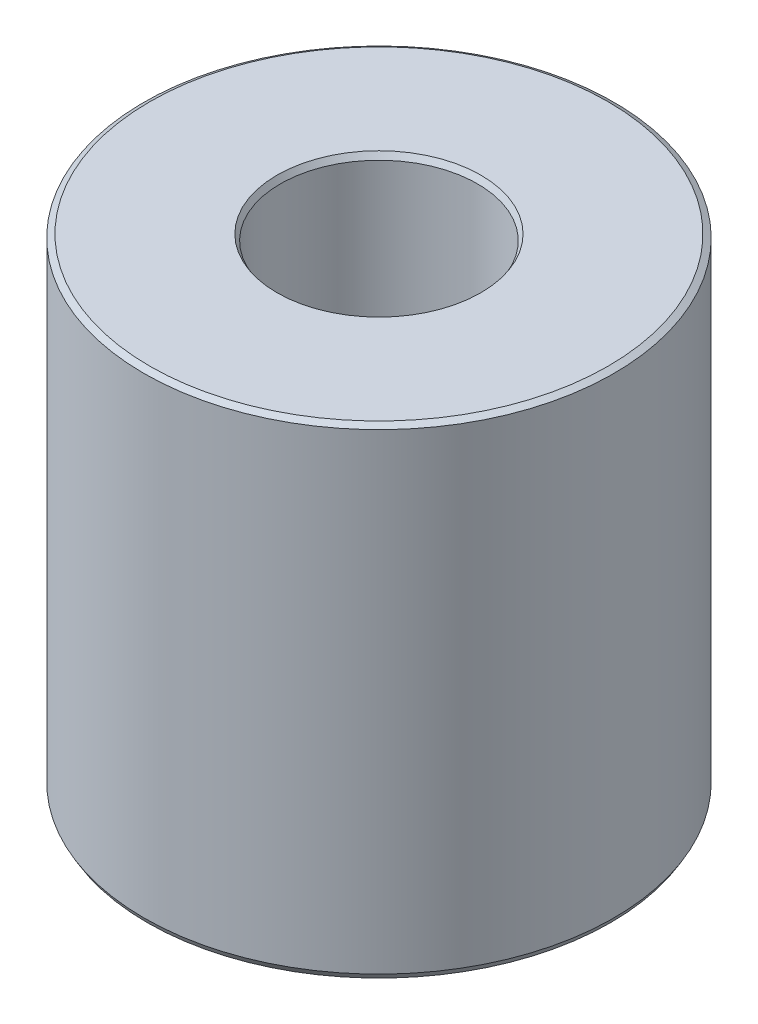
SolidWorks part; units mm, degrees
ref_plane "Front Plane" through (0, 0, 0) normal (0, 0, 1) x (1, 0, 0)
ref_plane "Top Plane" through (0, 0, 0) normal (0, 1, 0) x (1, 0, 0)
ref_plane "Right Plane" through (0, 0, 0) normal (1, 0, 0) x (0, 0, -1)
sketch "Sketch1" plane through (0, 0, 0) normal (0, 1, 0) x (1, 0, 0)
  circle A0 centre (0, 0) radius 55
  dimension "SLEEVE_OD" = 110
extrude "Boss-Extrude1" add sketch "Sketch1" along normal blind 112.5364
sketch "Sketch2" plane through (0, 0, 0) normal (0, 1, 0) x (1, 0, 0)
  circle A0 centre (0, 0) radius 23.0704
  dimension "BORE_D" = 46.1409
extrude "Cut-Extrude1" cut sketch "Sketch2" along normal through all
chamfer "Chamfer1" distance 0.7885 angle 60 4 edges at (0, 112.5364, 23.0704) (0, 0, 23.0704) (0, 0, 55) (0, 112.5364, 55) first distance on face at (0, 112.5364, 23.0704) first distance on face at (0, 0, 23.0704) first distance on face at (0, 112.5364, 55)
